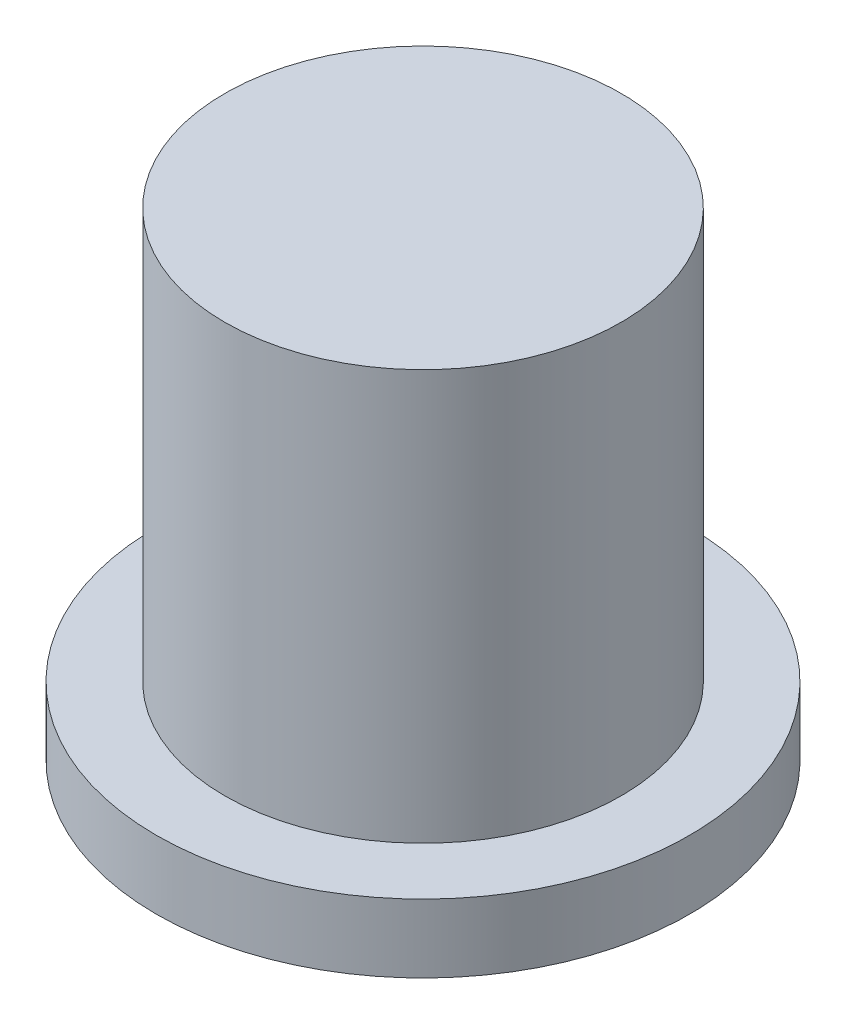
SolidWorks part; units mm, degrees
ref_plane "前视基准面" through (0, 0, 0) normal (0, 0, 1) x (1, 0, 0)
ref_plane "上视基准面" through (0, 0, 0) normal (0, 1, 0) x (1, 0, 0)
ref_plane "右视基准面" through (0, 0, 0) normal (1, 0, 0) x (0, 0, -1)
other "Configuration Table"
sketch "草图1" plane through (0, 0, 0) normal (0, 1, 0) x (1, 0, 0)
  circle A0 centre (0, 0) radius 2.9
  circle A1 centre (0, 0) radius 1.9
  circle A2 centre (0, 0) radius 3.9
  dimension "D1" = 3.8
  dimension "D2" = 1
  dimension "D3" = 1
extrude "凸台-拉伸1" add sketch "草图1" along normal blind 6 contours A0 | A1
extrude "凸台-拉伸2" add sketch "草图1<7>" along normal blind 1 from surface contours A0 starting at face at (0, 6, 2.9)
sketch "草图1<7>" plane through (0, 0, 0) normal (0, 1, 0) x (1, 0, 0) same geometry as "草图1"
extrude "凸台-拉伸3" add sketch "草图1<8>" along normal blind 1 contours A2 | A1
sketch "草图1<8>" plane through (0, 0, 0) normal (0, 1, 0) x (1, 0, 0) same geometry as "草图1"
